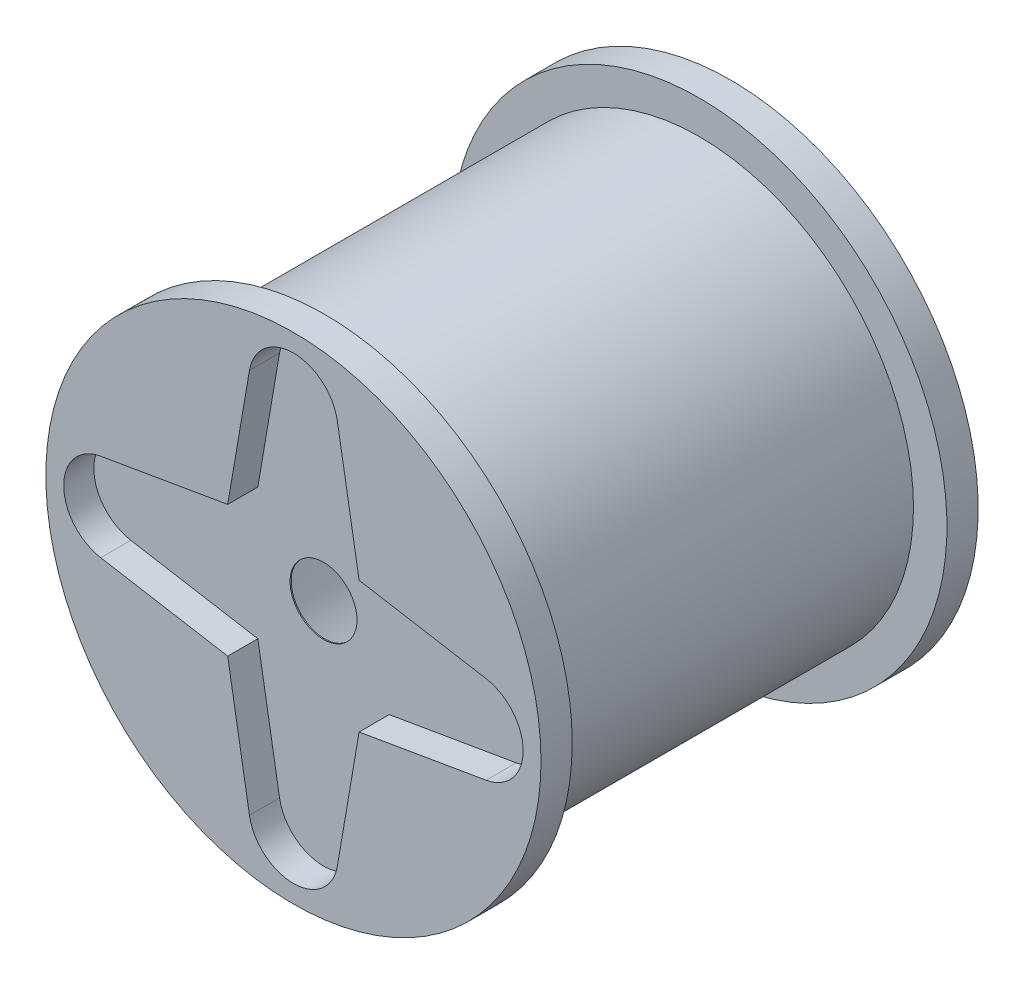
SolidWorks part; units mm, degrees
ref_plane "Ebene vorne" through (0, 0, 0) normal (0, 0, 1) x (1, 0, 0)
ref_plane "Ebene oben" through (0, 0, 0) normal (0, 1, 0) x (1, 0, 0)
ref_plane "Ebene rechts" through (0, 0, 0) normal (1, 0, 0) x (0, 0, -1)
sketch "Skizze1" plane through (0, 0, 0) normal (0, 0, 1) x (1, 0, 0)
  circle A0 centre (0, 0) radius 9.6
  dimension "D1" = 19.2
extrude "Aufsatz-Linear austragen1" add sketch "Skizze1" along normal blind 9.8 and the other way blind 9.8
ref_axis "Rotationsachse" [suppressed] through (0, 0, -9.8) along (0, 0, 1)
sketch "Skizze2" plane through (0, 0, 9.8) normal (0, 0, 1) x (1, 0, 0)
  circle A0 centre (0, 0) radius 11.1
  dimension "D1" = 22.2
extrude "Aufsatz-Linear austragen2" add sketch "Skizze2" against normal blind 1.4
sketch "Skizze3" plane through (0, 0, -9.8) normal (0, 0, -1) x (-1, 0, 0)
  circle A0 centre (0, 0) radius 11.1
  dimension "D1" = 22.2
extrude "Aufsatz-Linear austragen3" add sketch "Skizze3" against normal blind 1.4
sketch "Skizze4" plane through (0, 0, 9.8) normal (0, 0, 1) x (1, 0, 0)
  line L0 (-3.3513, 0.5735) -> (-1.9713, 8.6373)
  line L1 (3.3513, 0.5735) -> (1.9713, 8.6373)
  circle A0 centre (0, 0) radius 3.4
  circle A1 centre (0, 8.3) radius 2
  dimension "D1" = 6.8
  dimension "D3" = 4
  dimension "D2" = 8.3
extrude "Schnitt-Linear austragen1" cut sketch "Skizze4" against normal blind 1.35 contours A1 | A1 L0 A0 L1 | A0 region at (0, 4.7309, 9.8) region at (0, 0, 9.8) region at (0, 8.3, 9.8)
pattern_circular "Kreismuster1" count 4 over 360 about axis through (0, 0, -9.8) along (0, 0, 1) of "Schnitt-Linear austragen1"
sketch "Skizze8" plane through (0, 0, 0) normal (1, 0, 0) x (0, 0, -1)
  line L0 (9.8, 0) -> (9.8, 8)
  line L1 (9.8, -11.1) -> (9.8, 11.1) construction
  line L2 (9.8, 8) -> (8.4, 8)
  line L3 (8.4, 11.1) -> (8.4, -11.1) construction
  line L4 (8.4, 8) -> (-8.4, 3.5)
  line L5 (-8.4, -9.6) -> (-8.4, 9.6) construction
  line L6 (-8.4, 3.5) -> (-8.4, 0)
  line L7 (-8.4, 0) -> (9.8, 0)
  dimension "D1" = 8
  dimension "D2" = 3.5
revolve "Schnitt-Rotation1" cut sketch "Skizze8" angle 360 about axis through (0, 0, -9.8) along (0, 0, 1)
sketch "Skizze9" plane through (0, 0, 8.45) normal (0, 0, 1) x (1, 0, 0)
  circle A0 centre (0, 0) radius 1.5
  dimension "D1" = 3
extrude "Schnitt-Linear austragen2" cut sketch "Skizze9" against normal blind 1.2
